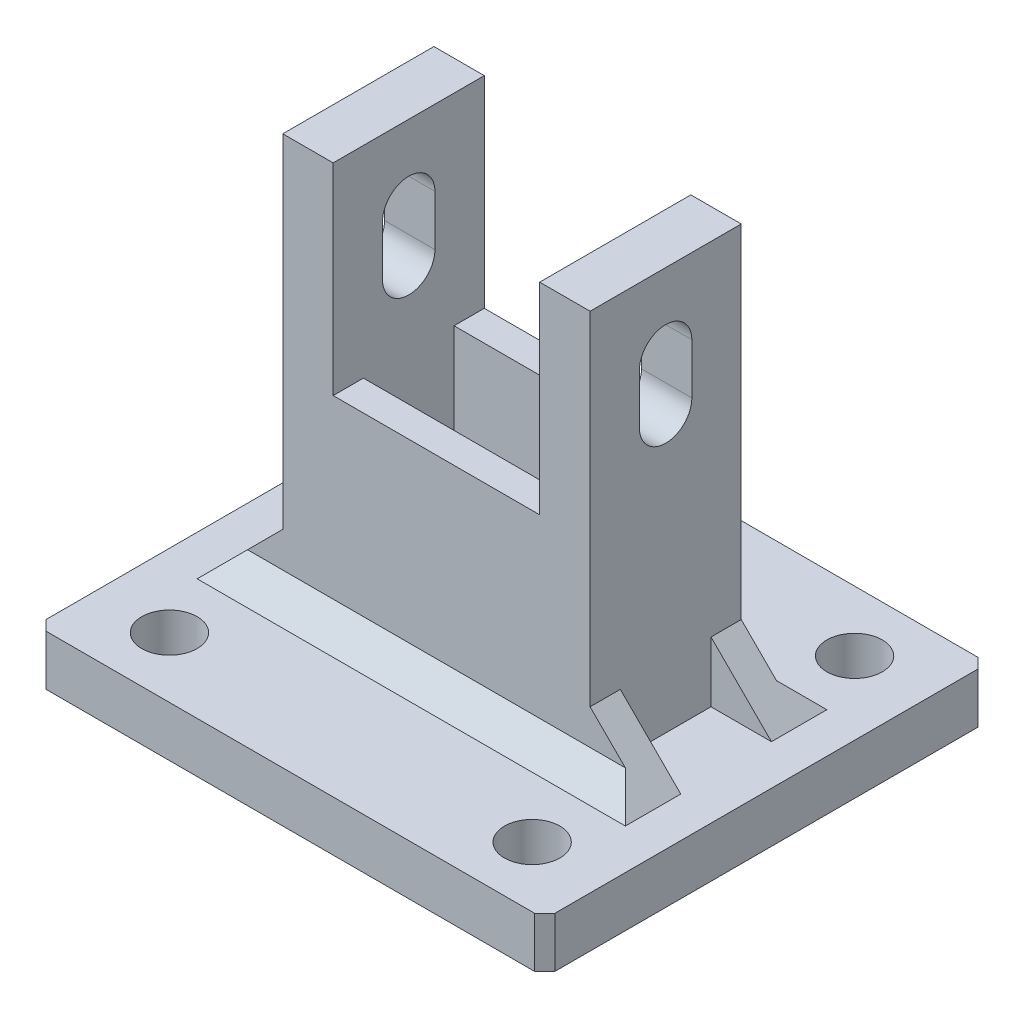
SolidWorks part; units mm, degrees
ref_plane "Front Plane" through (0, 0, 0) normal (0, 0, 1) x (1, 0, 0)
ref_plane "Top Plane" through (0, 0, 0) normal (0, 1, 0) x (1, 0, 0)
ref_plane "Right Plane" through (0, 0, 0) normal (1, 0, 0) x (0, 0, -1)
sketch "Sketch1" plane through (0, 0, 0) normal (0, 1, 0) x (1, 0, 0)
  line L1 (-18, 16) -> (18, 16) construction
  line L2 (-18, 16) -> (-18, -16) construction
  line L3 (-18, -16) -> (18, -16) construction
  line L4 (18, 16) -> (18, -16) construction
  line L5 (-18, 16) -> (18, -16) construction
  line L6 (-18, -16) -> (18, 16) construction
  line L7 (-25.25, 22) -> (25.25, 22)
  line L8 (-25.25, 22) -> (-25.25, -22)
  line L9 (-25.25, -22) -> (25.25, -22)
  line L10 (25.25, 22) -> (25.25, -22)
  line L11 (-25.25, 22) -> (25.25, -22) construction
  line L12 (-25.25, -22) -> (25.25, 22) construction
  circle A0 centre (-18, 16) radius 2.75
  circle A1 centre (18, 16) radius 2.75
  circle A2 centre (18, -16) radius 2.75
  circle A3 centre (-18, -16) radius 2.75
  point P0 (0, 0)
  point P10 (0, 0)
  dimension "D3" = 5.5
  dimension "D1" = 32
  dimension "D2" = 36
  dimension "D4" = 50.5
  dimension "D5" = 44
extrude "Boss-Extrude1" add sketch "Sketch1" along normal blind 5
sketch "Sketch3" plane through (0, 0, 22) normal (0, 0, 1) x (1, 0, 0)
  line L0 (-25.25, 5) -> (25.25, 5) construction
  line L1 (-15.25, 5) -> (-10.25, 5)
  line L2 (-15.25, 5) -> (-15.25, 45)
  line L3 (-15.25, 45) -> (-10.25, 45)
  line L4 (-10.25, 5) -> (-10.25, 45)
  line L6 (10.25, 5) -> (15.25, 5)
  line L7 (10.25, 5) -> (10.25, 45)
  line L8 (10.25, 45) -> (15.25, 45)
  line L9 (15.25, 5) -> (15.25, 45)
  line L10 (0, 0) -> (0, -8.4132) construction
  dimension "D1" = 5
  dimension "D2" = 20.5
  dimension "D3" = 40
extrude "Boss-Extrude2" add sketch "Sketch3" against normal blind 15 from offset 14.5 offset against normal yes
sketch "Sketch4" plane through (15.25, 0, 0) normal (1, 0, 0) x (0, 0, -1)
  line L0 (0, 37.5) -> (0, 32.5) construction
  line L1 (2.6, 37.5) -> (2.6, 32.5)
  line L2 (-2.6, 37.5) -> (-2.6, 32.5)
  line L3 (7.5, 45) -> (-7.5, 45) construction
  arc A0 (2.6, 37.5) -> (-2.6, 37.5) centre (0, 37.5) ccw
  arc A1 (-2.6, 32.5) -> (2.6, 32.5) centre (0, 32.5) ccw
  point P3 (0, 35)
  dimension "D2" = 2.6
  dimension "D1" = 5
  dimension "D3" = 10
extrude "Cut-Extrude1" cut sketch "Sketch4" against normal up to surface (30.5 mm away) up to face at (-15.25, 25, 0)
sketch "Sketch5" plane through (0, 0, 7.5) normal (0, 0, 1) x (1, 0, 0)
  line L0 (15.25, 11) -> (21.25, 5)
  line L1 (15.25, 5) -> (15.25, 45) construction
  line L2 (-25.25, 5) -> (25.25, 5) construction
  line L3 (21.25, 5) -> (15.25, 5)
  line L4 (15.25, 5) -> (15.25, 11)
  line L5 (0, -1.6344) -> (0, 7.9357) construction
  line L6 (-21.25, 5) -> (-15.25, 5)
  line L7 (-15.25, 11) -> (-21.25, 5)
  line L8 (-15.25, 5) -> (-15.25, 11)
  line L17 (-10.25, 5) -> (-10.25, 45) construction
  line L18 (-10.25, 25) -> (10.25, 25)
  line L19 (-10.25, 25) -> (-10.25, 5)
  line L20 (-10.25, 5) -> (10.25, 5)
  line L21 (10.25, 25) -> (10.25, 5)
  dimension "D1" = 45
  dimension "D2" = 6
  dimension "D3" = 20
extrude "Boss-Extrude3" add sketch "Sketch5" against normal blind 3
ref_plane "Plane1" through (0, 0, 0) normal (0, 0, -1) x (-1, 0, 0)
mirror "Mirror1" about plane through (0, 0, 0) normal (0, 0, -1) of "Boss-Extrude3"
chamfer "Chamfer2" distance 1 angle 45 4 edges at (25.25, 2.5, 22) (-25.25, 2.5, -22) (25.25, 2.5, -22) (-25.25, 2.5, 22)
chamfer "Chamfer3" distance 2.5 angle 45 2 edges at (0, 5, -7.5) (0, 5, 7.5)
